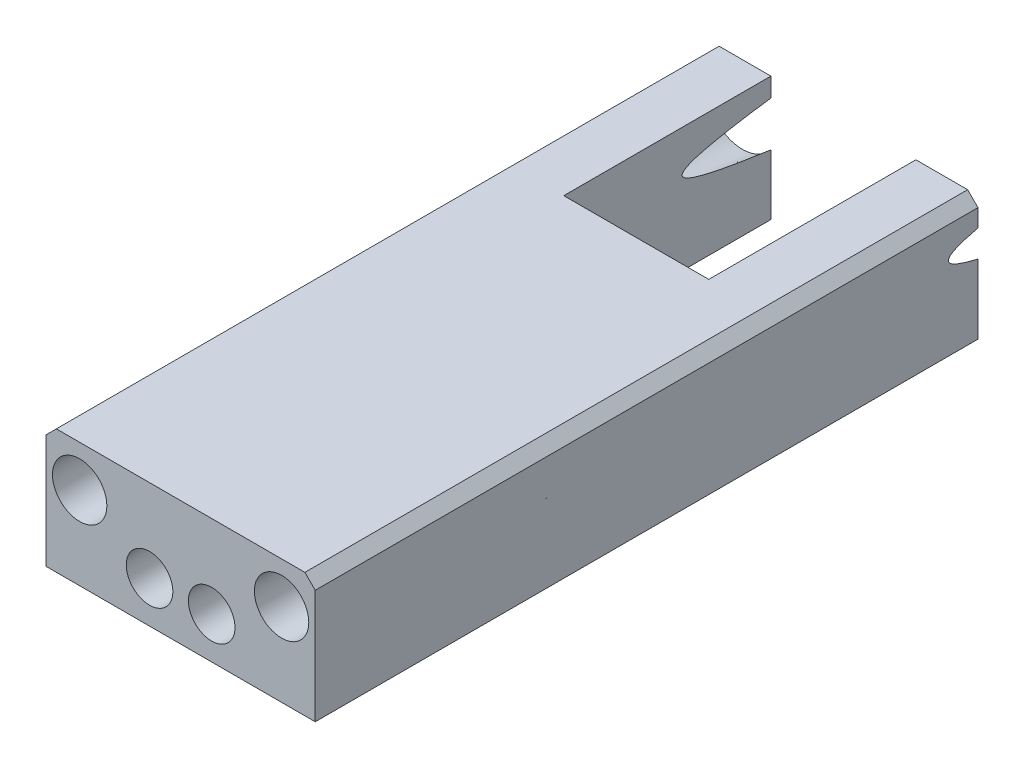
SolidWorks part; units mm, degrees
ref_plane "Front Plane" through (0, 0, 0) normal (0, 0, 1) x (1, 0, 0)
ref_plane "Top Plane" through (0, 0, 0) normal (0, 1, 0) x (1, 0, 0)
ref_plane "Right Plane" through (0, 0, 0) normal (1, 0, 0) x (0, 0, -1)
sketch "Sketch1" plane through (0, 0, 0) normal (0, 0, 1) x (1, 0, 0)
  line L0 (0, 0) -> (26, 0)
  line L1 (26, 0) -> (26, 8)
  line L2 (26, 8) -> (25.375, 8)
  line L3 (0, 8) -> (0, 0)
  line L4 (0.625, 8) -> (0, 8)
  line L5 (20.125, 8) -> (5.875, 8)
  arc A0 (0.625, 8) -> (5.875, 8) centre (3.25, 8) ccw
  arc A1 (20.125, 8) -> (25.375, 8) centre (22.75, 8) ccw
  dimension "D3" = 5.25
  dimension "D4" = 5.25
  dimension "D5" = 3.25
  dimension "D6" = 3.25
  dimension "D1" = 26
  dimension "D2" = 8
extrude "Boss-Extrude1" add sketch "Sketch1" along normal blind 44
sketch "Sketch2" plane through (0, 0, 44) normal (0, 0, 1) x (1, 0, 0)
  line L0 (0, 4) -> (26, 4) construction
  line L3 (0, 0) -> (26, 0) construction
  line L4 (0, 8) -> (0, 0) construction
  line L5 (26, 0) -> (26, 8) construction
  circle A0 centre (10, 4) radius 2.25
  circle A1 centre (16, 4) radius 2.25
  point P2 (13, 0)
  dimension "D1" = 4.5
  dimension "D2" = 4.5
  dimension "D3" = 3
  dimension "D4" = 6
  dimension "D5" = 4
extrude "Cut-Extrude1" cut sketch "Sketch2" against normal through all
sketch "Sketch4" plane through (0, 0, 0) normal (0, 0, -1) x (-1, 0, 0)
  line L0 (-6, 8) -> (-6, 0)
  line L1 (-20.125, 8) -> (-5.875, 8) construction
  line L2 (0, 0) -> (-26, 0) construction
  line L3 (-6, 0) -> (0, 0)
  line L4 (0, 0) -> (0, 8)
  line L5 (0, 8) -> (-0.625, 8)
  line L6 (-6, 8) -> (-5.875, 8)
  line L7 (-20, 8) -> (-20, 0)
  line L8 (-20, 0) -> (-26, 0)
  line L9 (-26, 0) -> (-26, 8)
  line L10 (-26, 8) -> (-25.375, 8)
  line L11 (-20.125, 8) -> (-20, 8)
  arc A0 (-5.875, 8) -> (-0.625, 8) centre (-3.25, 8) ccw
  arc A1 (-25.375, 8) -> (-20.125, 8) centre (-22.75, 8) ccw
  arc A2 (-25.375, 8) -> (-20.125, 8) centre (-22.75, 8) ccw construction
  dimension "D1" = 6
  dimension "D2" = 2.625
  dimension "D3" = 6
extrude "Boss-Extrude2" add sketch "Sketch4" along normal blind 20
sketch "Sketch5" plane through (0, 0, 44) normal (0, 0, 1) x (1, 0, 0)
  line L0 (0, 8) -> (0, 12)
  line L1 (0, 12) -> (26, 12)
  line L2 (26, 12) -> (26, 8)
  line L3 (0, 8) -> (0.625, 8)
  line L4 (26, 8) -> (25.375, 8)
  line L5 (5.875, 8) -> (20.125, 8)
  arc A0 (5.875, 8) -> (0.625, 8) centre (3.25, 8) ccw
  arc A1 (25.375, 8) -> (20.125, 8) centre (22.75, 8) ccw
  dimension "D1" = 4
extrude "Boss-Extrude3" add sketch "Sketch5" against normal up to surface (64 mm away) up to face at (3.0833, 4.8958, -20)
sketch "Sketch6" plane through (0, 8, 0) normal (0, -1, 0) x (1, 0, 0)
  line L0 (26, -20) -> (20, -20) construction
  line L1 (6, 0) -> (20, 0)
  line L2 (6, 0) -> (6, -20)
  line L3 (6, -20) -> (20, -20)
  line L4 (20, 0) -> (20, -20)
  line L5 (20, -20) -> (20, 0) construction
extrude "Cut-Extrude2" cut sketch "Sketch6" against normal through all
chamfer "Chamfer1" distance 10 angle 5 2 edges at (20.125, 8, -20) (0.625, 8, -20) first distance on face at (20.125, 8, -20) first distance on face at (0.625, 8, -20)
chamfer "Chamfer2" distance 1 angle 45 2 edges at (0, 12, 12) (26, 12, 12)
